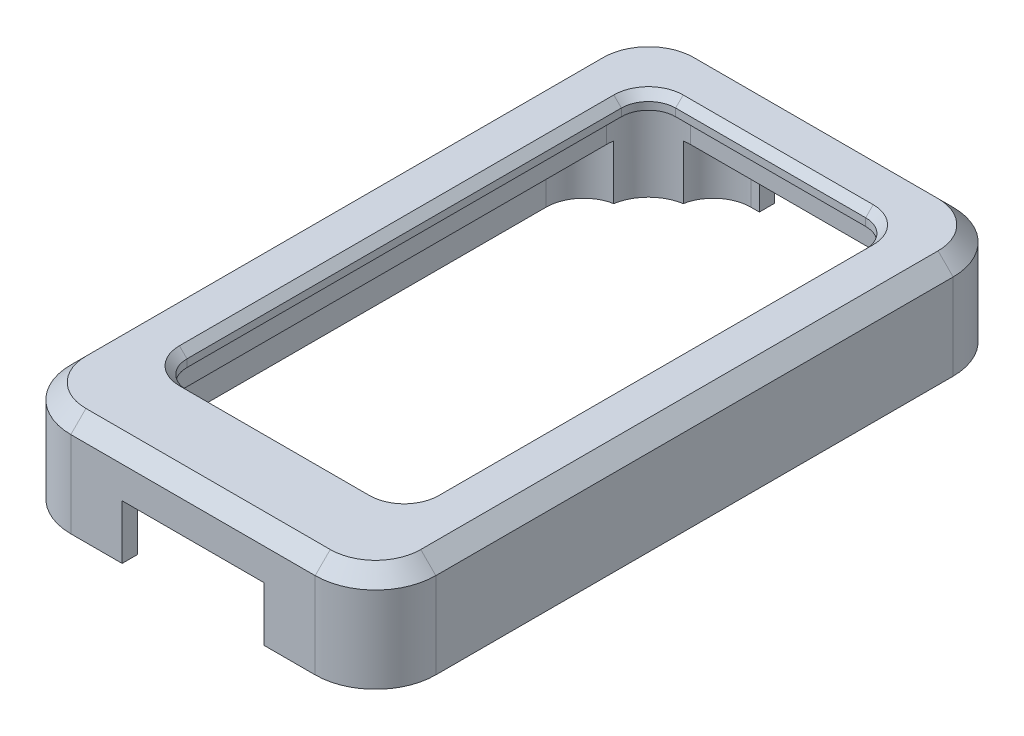
SolidWorks part; units mm, degrees
ref_plane "前视基准面" through (0, 0, 0) normal (0, 0, 1) x (1, 0, 0)
ref_plane "上视基准面" through (0, 0, 0) normal (0, 1, 0) x (1, 0, 0)
ref_plane "右视基准面" through (0, 0, 0) normal (1, 0, 0) x (0, 0, -1)
other "Configuration Table"
sketch "草图5" plane through (0, 0, 0) normal (0, 1, 0) x (1, 0, 0)
  line L1 (-9.1, -18.15) -> (9.1, -18.15)
  line L2 (-9.1, -18.15) -> (-9.1, 18.15)
  line L3 (-9.1, 18.15) -> (9.1, 18.15)
  line L4 (9.1, -18.15) -> (9.1, 18.15)
  line L5 (0, 18.15) -> (0, -18.15) construction
  line L6 (-9.1, 0) -> (9.1, 0) construction
  point P0 (0, 0)
  dimension "D1" = 18.2
  dimension "D2" = 36.3
sketch "草图1" plane through (0, 0, 0) normal (0, 1, 0) x (1, 0, 0)
  line L0 (-9.1, 18.15) -> (9.1, 18.15) construction
  line L1 (-12.1, -21.15) -> (12.1, -21.15)
  line L2 (-12.1, -21.15) -> (-12.1, 21.15)
  line L3 (-12.1, 21.15) -> (12.1, 21.15)
  line L4 (12.1, -21.15) -> (12.1, 21.15)
  line L5 (0, 21.15) -> (0, -21.15) construction
  line L6 (-12.1, 0) -> (12.1, 0) construction
  line L7 (-9.1, -18.15) -> (-9.1, 18.15) construction
  point P0 (0, 0)
  dimension "D1" = 3
  dimension "D2" = 3
extrude "凸台-拉伸1" add sketch "草图1" along normal blind 6.7
fillet "圆角1" radius 4 4 edges at (12.1, 3.35, 21.15) (-12.1, 3.35, -21.15) (12.1, 3.35, -21.15) (-12.1, 3.35, 21.15)
sketch "草图2" plane through (0, 0, 0) normal (0, -1, 0) x (1, 0, 0)
  line L1 (-6.3, -18.15) -> (6.3, -18.15)
  line L2 (-9.1, -15.35) -> (-9.1, 15.35)
  line L3 (-6.3, 18.15) -> (6.3, 18.15)
  line L4 (9.1, -15.35) -> (9.1, 15.35)
  line L5 (0, 18.15) -> (0, -18.15) construction
  line L6 (-9.1, 0) -> (9.1, 0) construction
  line L8 (-9.1, 18.15) -> (9.1, 18.15) construction
  line L9 (-9.1, 18.15) -> (-9.1, -18.15) construction
  arc A0 (6.3, -18.15) -> (9.1, -15.35) centre (6.3, -15.35) ccw
  arc A1 (-6.3, -18.15) -> (-9.1, -15.35) centre (-6.3, -15.35) cw
  arc A2 (6.3, 18.15) -> (9.1, 15.35) centre (6.3, 15.35) cw
  arc A3 (-9.1, 15.35) -> (-6.3, 18.15) centre (-6.3, 15.35) cw
  point P0 (0, 0)
  point P9 (-9.1, -18.15)
  point P12 (9.1, 18.15)
  point P15 (-9.1, 18.15)
  point P16 (7.7227, 16.7727)
  point P19 (6.0031, 15.0531)
  point P21 (5.6622, 14.7122)
  point P23 (0, 0)
  point P24 (5.8538, 14.9038)
  dimension "D1" = 2.8
extrude "切除-拉伸1" cut sketch "草图2" against normal offset from surface (5.7 mm away) 1 up to face at (0, 6.7, 0)
sketch "草图3" plane through (0, 5.7, 0) normal (0, -1, 0) x (1, 0, 0)
  line L0 (-9.1, -18.15) -> (9.1, -18.15) construction
  line L1 (-6.3, -17.15) -> (6.3, -17.15)
  line L2 (-8.1, -15.35) -> (-8.1, 13.45)
  line L3 (-6.3, 15.25) -> (6.3, 15.25)
  line L4 (8.1, -15.35) -> (8.1, 13.45)
  line L5 (0, 15.25) -> (0, -17.15) construction
  line L6 (-8.1, -0.95) -> (8.1, -0.95) construction
  arc A0 (-8.1, 13.45) -> (-6.3, 15.25) centre (-6.3, 13.45) cw
  arc A1 (6.3, 15.25) -> (8.1, 13.45) centre (6.3, 13.45) cw
  arc A2 (6.3, -17.15) -> (8.1, -15.35) centre (6.3, -15.35) ccw
  arc A3 (-6.3, -17.15) -> (-8.1, -15.35) centre (-6.3, -15.35) cw
  arc A4 (6.3, -18.15) -> (9.1, -15.35) centre (6.3, -15.35) ccw construction
  arc A5 (-9.1, -15.35) -> (-6.3, -18.15) centre (-6.3, -15.35) ccw construction
  point P0 (0, -0.95)
  point P13 (0, 0)
  dimension "D1" = 1
  dimension "D2" = 32.4
extrude "切除-拉伸2" cut sketch "草图3" against normal through all
chamfer "倒角1" distance 0.5 angle 45 8 edges at (-7.5728, 6.7, 14.7228) (-8.1, 6.7, -0.95) (0, 6.7, 15.25) (-7.5728, 6.7, -16.6228) (7.5728, 6.7, 14.7228) (0, 6.7, -17.15) (8.1, 6.7, -0.95) (7.5728, 6.7, -16.6228)
chamfer "倒角2" distance 1 angle 45 8 edges at (10.9284, 6.7, 19.9784) (12.1, 6.7, 0) (0, 6.7, 21.15) (10.9284, 6.7, -19.9784) (-10.9284, 6.7, 19.9784) (0, 6.7, -21.15) (-12.1, 6.7, 0) (-10.9284, 6.7, -19.9784)
sketch "草图4" plane through (0, 0, 0) normal (0, -1, 0) x (1, 0, 0)
  line L0 (11.1, -17.15) -> (11.1, 17.15)
  line L1 (8.1, 20.15) -> (-8.1, 20.15)
  line L2 (-11.1, 17.15) -> (-11.1, -17.15)
  line L3 (-8.1, -20.15) -> (8.1, -20.15)
  line L4 (12.1, -17.15) -> (12.1, 17.15)
  line L5 (8.1, 21.15) -> (-8.1, 21.15)
  line L6 (-12.1, 17.15) -> (-12.1, -17.15)
  line L7 (-8.1, -21.15) -> (8.1, -21.15)
  line L8 (12.1, -17.15) -> (12.1, 17.15) construction
  line L9 (8.1, 21.15) -> (-8.1, 21.15) construction
  line L10 (-12.1, 17.15) -> (-12.1, -17.15) construction
  line L11 (-8.1, -21.15) -> (8.1, -21.15) construction
  arc A0 (11.1, 17.15) -> (8.1, 20.15) centre (8.1, 17.15) ccw
  arc A1 (-8.1, 20.15) -> (-11.1, 17.15) centre (-8.1, 17.15) ccw
  arc A2 (-11.1, -17.15) -> (-8.1, -20.15) centre (-8.1, -17.15) ccw
  arc A3 (8.1, -20.15) -> (11.1, -17.15) centre (8.1, -17.15) ccw
  arc A4 (12.1, 17.15) -> (8.1, 21.15) centre (8.1, 17.15) ccw
  arc A5 (-8.1, 21.15) -> (-12.1, 17.15) centre (-8.1, 17.15) ccw
  arc A6 (-12.1, -17.15) -> (-8.1, -21.15) centre (-8.1, -17.15) ccw
  arc A7 (8.1, -21.15) -> (12.1, -17.15) centre (8.1, -17.15) ccw
  arc A8 (12.1, 17.15) -> (8.1, 21.15) centre (8.1, 17.15) ccw construction
  arc A9 (-8.1, 21.15) -> (-12.1, 17.15) centre (-8.1, 17.15) ccw construction
  arc A10 (-12.1, -17.15) -> (-8.1, -21.15) centre (-8.1, -17.15) ccw construction
  arc A11 (8.1, -21.15) -> (12.1, -17.15) centre (8.1, -17.15) ccw construction
  dimension "D1" = 0
  dimension "D2" = 1
extrude "切除-拉伸3" cut sketch "草图4" against normal offset from surface (3.6 mm away) 2.1 up to face at (0, 5.7, -0.95)
sketch "草图7" plane through (0, 3.6, 0) normal (0, -1, 0) x (1, 0, 0)
  line L6 (8.1, 20.15) -> (-8.1, 20.15) construction
  line L7 (-11.1, -15.8081) -> (-6.7581, -15.8081) construction
  line L8 (-11.1, -15.8081) -> (-11.1, -20.15) construction
  line L9 (-11.1, -20.15) -> (-6.7581, -20.15) construction
  line L10 (-6.7581, -15.8081) -> (-6.7581, -20.15) construction
  line L11 (6.7581, -20.15) -> (11.1, -20.15) construction
  line L12 (6.7581, -20.15) -> (6.7581, -15.8081) construction
  line L13 (6.7581, -15.8081) -> (11.1, -15.8081) construction
  line L14 (11.1, -20.15) -> (11.1, -15.8081) construction
  line L15 (6.7581, 20.15) -> (11.1, 20.15) construction
  line L24 (6.7581, 20.15) -> (8.1, 20.15)
  line L25 (8.1, 20.15) -> (-8.1, 20.15)
  line L26 (-11.1, 17.15) -> (-11.1, -17.15)
  line L27 (-8.1, -20.15) -> (8.1, -20.15)
  line L28 (11.1, -17.15) -> (11.1, 17.15)
  line L39 (-6.7581, 20.15) -> (-8.1, 20.15)
  line L40 (-11.1, 17.15) -> (-11.1, 15.8081)
  line L41 (-8.1, -20.15) -> (-6.7581, -20.15)
  line L42 (11.1, -17.15) -> (11.1, -15.8081)
  line L48 (6.7581, 20.15) -> (6.7581, 15.8081) construction
  line L49 (6.7581, 15.8081) -> (11.1, 15.8081) construction
  line L50 (11.1, 20.15) -> (11.1, 15.8081) construction
  line L51 (-11.1, -15.8081) -> (-9.0623, -15.8081)
  line L52 (-11.1, 15.8081) -> (-6.7581, 15.8081) construction
  line L53 (-11.1, 15.8081) -> (-11.1, 20.15) construction
  line L54 (-11.1, 20.15) -> (-6.7581, 20.15) construction
  line L55 (-6.7581, 15.8081) -> (-6.7581, 20.15) construction
  line L56 (-6.7581, -20.15) -> (-6.7581, -18.1123)
  line L57 (6.7581, -20.15) -> (6.7581, -18.1123)
  line L58 (9.0623, -15.8081) -> (11.1, -15.8081)
  line L59 (11.1, 15.8081) -> (9.0623, 15.8081)
  line L60 (6.7581, 20.15) -> (6.7581, 18.1123)
  line L61 (-6.7581, 20.15) -> (-6.7581, 18.1123)
  line L62 (-11.1, 15.8081) -> (-9.0623, 15.8081)
  line L63 (6.7581, 20.15) -> (-6.7581, 20.15) construction
  line L64 (6.7581, 20.15) -> (6.3, 20.15) construction
  line L65 (11.1, -15.8081) -> (11.1, 15.8081) construction
  line L66 (11.1, 15.8081) -> (11.1, 17.15)
  line L67 (-6.7581, -20.15) -> (6.7581, -20.15) construction
  line L68 (6.7581, -20.15) -> (8.1, -20.15)
  line L69 (-11.1, 15.8081) -> (-11.1, -15.8081) construction
  line L70 (-11.1, -15.8081) -> (-11.1, -17.15)
  arc A0 (-6.3, 18.15) -> (-9.1, 15.35) centre (-6.3, 15.35) ccw construction
  arc A1 (-6.7581, 18.1123) -> (-9.0623, 15.8081) centre (-6.3, 15.35) ccw
  arc A2 (9.1, 15.35) -> (6.3, 18.15) centre (6.3, 15.35) ccw construction
  arc A3 (-9.1, -15.35) -> (-6.3, -18.15) centre (-6.3, -15.35) ccw construction
  arc A4 (6.3, -18.15) -> (9.1, -15.35) centre (6.3, -15.35) ccw construction
  arc A5 (-9.0623, -15.8081) -> (-6.7581, -18.1123) centre (-6.3, -15.35) ccw
  arc A6 (6.7581, -18.1123) -> (9.0623, -15.8081) centre (6.3, -15.35) ccw
  arc A7 (9.0623, 15.8081) -> (6.7581, 18.1123) centre (6.3, 15.35) ccw
  arc A25 (-6.7581, -18.1123) -> (-6.3, -18.15) centre (-6.3, -15.35) ccw construction
  arc A26 (-8.1, 20.15) -> (-11.1, 17.15) centre (-8.1, 17.15) ccw
  arc A27 (-11.1, -17.15) -> (-8.1, -20.15) centre (-8.1, -17.15) ccw
  arc A28 (8.1, -20.15) -> (11.1, -17.15) centre (8.1, -17.15) ccw
  arc A29 (11.1, 17.15) -> (8.1, 20.15) centre (8.1, 17.15) ccw
  arc A30 (-9.1, -15.35) -> (-9.0623, -15.8081) centre (-6.3, -15.35) ccw construction
  arc A34 (-8.1, 20.15) -> (-11.1, 17.15) centre (-8.1, 17.15) ccw
  arc A35 (-11.1, -17.15) -> (-8.1, -20.15) centre (-8.1, -17.15) ccw
  arc A36 (8.1, -20.15) -> (11.1, -17.15) centre (8.1, -17.15) ccw
  arc A37 (11.1, 17.15) -> (8.1, 20.15) centre (8.1, 17.15) ccw
  arc A42 (9.0623, -15.8081) -> (9.1, -15.35) centre (6.3, -15.35) ccw construction
  arc A43 (6.3, -18.15) -> (6.7581, -18.1123) centre (6.3, -15.35) ccw construction
  arc A44 (-6.3, 18.15) -> (-6.7581, 18.1123) centre (-6.3, 15.35) ccw construction
  arc A45 (6.7581, 18.1123) -> (6.3, 18.15) centre (6.3, 15.35) ccw construction
  arc A46 (9.1, 15.35) -> (9.0623, 15.8081) centre (6.3, 15.35) ccw construction
  arc A47 (-9.0623, 15.8081) -> (-9.1, 15.35) centre (-6.3, 15.35) ccw construction
  arc A48 (9.1, 15.35) -> (6.3, 18.15) centre (6.3, 15.35) ccw construction
  point P3 (-6.7581, 18.0301)
  point P48 (6.7581, 18.1123)
  point P52 (-6.7581, 18.1164)
  dimension "D2" = 4.3419
  dimension "D1" = 0
extrude "凸台-拉伸2" add sketch "草图7" along normal up to surface (3.6 mm away) up to face at (0, 0, 0)
sketch "草图12" plane through (0, 0, 0) normal (0, -1, 0) x (-1, 0, 0)
  line L1 (-9.6, -18.65) -> (9.6, -18.65) construction
  line L2 (-9.6, -18.65) -> (-9.6, 18.65) construction
  line L3 (-9.6, 18.65) -> (9.6, 18.65) construction
  line L4 (9.6, -18.65) -> (9.6, 18.65) construction
  line L5 (-12.1, -17.15) -> (-12.1, 17.15) construction
  line L6 (-8.1, 21.15) -> (8.1, 21.15) construction
  point P0 (-9.6, 18.65)
  point P2 (9.6, 18.65)
  point P4 (9.6, -18.65)
  point P6 (-9.6, -18.65)
  point P95 (-9.6612, 19.0447)
  point P96 (-9.5498, 18.8084)
  point P97 (9.9768, -18.6919)
  point P98 (0, -18.65)
  point P100 (9.6, 0)
  dimension "D1" = 2.5
  dimension "D2" = 2.5
sketch "草图13" plane through (0, 3.6, 0) normal (0, -1, 0) x (1, 0, 0)
  line L7 (6.7581, 18.1123) -> (6.7581, 20.15)
  line L12 (6.7581, 20.15) -> (-6.7581, 20.15)
  line L13 (-6.7581, 20.15) -> (-6.7581, 18.1123)
  line L14 (-6.3, 18.15) -> (6.3, 18.15)
  line L15 (6.7581, 18.1123) -> (6.7581, 20.15)
  line L16 (6.7581, 20.15) -> (-6.7581, 20.15)
  line L17 (-6.7581, 20.15) -> (-6.7581, 18.1123)
  line L18 (-6.3, 18.15) -> (6.3, 18.15)
  arc A6 (6.7581, 18.1123) -> (6.3, 18.15) centre (6.3, 15.35) ccw
  arc A7 (-6.3, 18.15) -> (-6.7581, 18.1123) centre (-6.3, 15.35) ccw
  arc A8 (6.7581, 18.1123) -> (6.3, 18.15) centre (6.3, 15.35) ccw
  arc A9 (-6.3, 18.15) -> (-6.7581, 18.1123) centre (-6.3, 15.35) ccw
  dimension "D1" = 0
extrude "切除-拉伸5" cut sketch "草图13" against normal up to surface (2.1 mm away) up to face at (0, 5.7, -0.95)
fillet "圆角4" radius 2.5 8 edges at (-11.1, 1.8, 15.8081) (-6.7581, 2.85, 20.15) (6.7581, 2.85, 20.15) (11.1, 1.8, 15.8081) (11.1, 1.8, -15.8081) (-11.1, 1.8, -15.8081) (6.7581, 1.8, -20.15) (-6.7581, 1.8, -20.15)
hole_wizard "M2x0.4 螺纹孔3" positions "草图12" profile "草图9" tap size "M2x0.4" standard "ANSI Metric"
sketch "草图9" plane through (9.6, 0, -18.65) normal (1, 0, 0) x (0, 0, -1)
  line L0 (0, 0) -> (0, 5.5)
  line L1 (0, 5.5) -> (0.8, 5.0193)
  line L2 (0.8, 5.0193) -> (0.8, 0)
  line L5 (0.8, 0) -> (0, 0)
  line L10 (0, 5.5) -> (-0.8, 5.0193) construction
  line L11 (0, -6.35) -> (0, 107.95) construction
  dimension "螺纹孔钻头直径" = 1.6
  dimension "螺纹孔钻头深度" = 5.5
  dimension "导头角度" = 118
cosmetic thread "孔螺纹线1" parameters "D1"=4, "D2"=2
cosmetic thread "孔螺纹线2" parameters "D1"=4, "D2"=2
cosmetic thread "孔螺纹线3" parameters "D1"=4, "D2"=2
cosmetic thread "孔螺纹线4" parameters "D1"=4, "D2"=2
sketch "草图14" plane through (0, 0, 0) normal (0, -1, 0) x (1, 0, 0)
  line L1 (-3.75, -20.15) -> (3.75, -20.15)
  line L2 (-3.75, -20.15) -> (-3.75, -21.15)
  line L3 (-3.75, -21.15) -> (3.75, -21.15)
  line L4 (3.75, -20.15) -> (3.75, -21.15)
  line L5 (8.1, -21.15) -> (-8.1, -21.15) construction
  line L6 (4.3012, -20.15) -> (-4.3012, -20.15) construction
  point P4 (-4, -20.1971)
  point P5 (-4, -20.15)
  point P8 (0, -20.15)
  point P10 (0, 0)
  dimension "D1" = 7.5
extrude "切除-拉伸6" cut sketch "草图14" against normal blind 3.6
sketch "草图15" plane through (0, 0, 0) normal (0, -1, 0) x (1, 0, 0)
  line L0 (-8.1, 21.15) -> (8.1, 21.15) construction
  line L1 (-4.7, 21.15) -> (4.7, 21.15)
  line L2 (-4.7, 21.15) -> (-4.7, 19.5554)
  line L3 (-4.7, 19.5554) -> (4.7, 19.5554)
  line L4 (4.7, 21.15) -> (4.7, 19.5554)
  point P8 (0, 21.15)
  dimension "D1" = 9.4
extrude "切除-拉伸7" cut sketch "草图15" against normal blind 3.6
